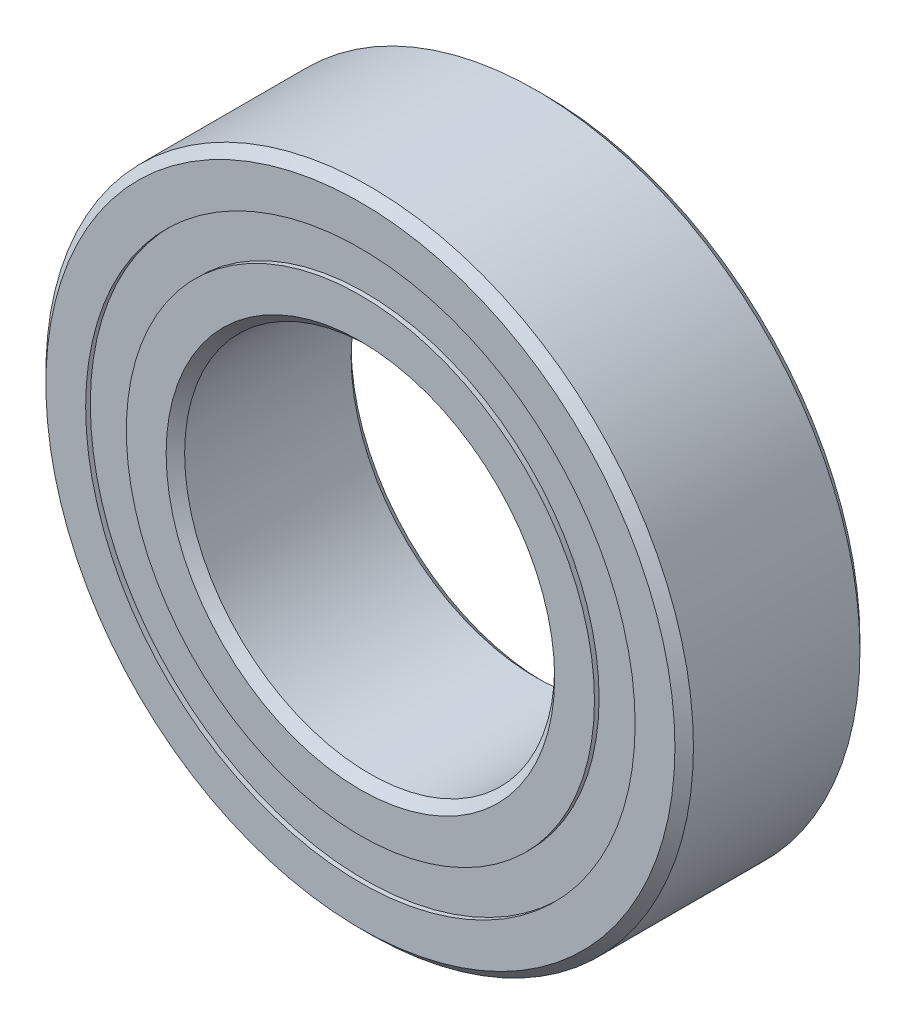
SolidWorks part; units mm, degrees
material "AISI 1015 Steel, Cold Drawn (SS)"
ref_plane "Front Plane" through (0, 0, 0) normal (0, 0, 1) x (1, 0, 0)
ref_plane "Top Plane" through (0, 0, 0) normal (0, 1, 0) x (1, 0, 0)
ref_plane "Right Plane" through (0, 0, 0) normal (1, 0, 0) x (0, 0, -1)
sketch "Sketch1" plane through (0, 0, 0) normal (1, 0, 0) x (0, 0, -1)
  line L0 (-2, 0) -> (2, 0) construction
  line L1 (0, 7) -> (0, -7) construction
  line L2 (1.8, 7) -> (-1.8, 7)
  line L3 (-1.8, 7) -> (-2, 6.8)
  line L4 (-2, 6.8) -> (-2, 5.9396)
  line L5 (-2, 5.9396) -> (-0.8889, 5.9396)
  line L6 (2, 5.9396) -> (0.8889, 5.9396)
  line L7 (2, 6.8) -> (2, 5.9396)
  line L8 (1.8, 7) -> (2, 6.8)
  line L9 (0, 7) -> (0, 5.5) construction
  line L10 (0, 5.5) -> (0, 4) construction
  arc A0 (-0.8889, 5.9396) -> (0.8889, 5.9396) centre (0, 5.5) cw
  point P14 (0, 4)
  dimension "D3" = 1.7778
  dimension "D1" = 45
  dimension "Width" = 4
  dimension "OD" = 14
  dimension "D2" = 0.2
  dimension "Shaft Dia" = 8
  dimension "D4" = 0.4396
revolve "Revolve1" add sketch "Sketch1" angle 360 about L0
sketch "Sketch3" plane through (0, 0, 0) normal (1, 0, 0) x (0, 0, -1)
  line L0 (-2, 5.0604) -> (-0.8889, 5.0604)
  line L1 (0, 7) -> (0, -7) construction
  line L2 (-2, 6.8) -> (-2, 5.9396) construction
  line L3 (-2, 5.0604) -> (-2, 4.2)
  line L4 (-1.8, 7) -> (-2, 6.8) construction
  line L5 (-2, 4.2) -> (-1.8, 4)
  line L6 (-1.8, 4) -> (1.8, 4)
  line L7 (1.8, 7) -> (1.8, -7) construction
  line L8 (1.8, 4) -> (2, 4.2)
  line L9 (2, -6.8) -> (2, 6.8) construction
  line L10 (2, 4.2) -> (2, 5.0604)
  line L11 (2, 5.0604) -> (0.8889, 5.0604)
  line L13 (1.8, 7) -> (2, 6.8) construction
  arc A0 (0.8889, 5.9396) -> (-0.8889, 5.9396) centre (0, 5.5) ccw construction
  arc A1 (0.8889, 5.0604) -> (-0.8889, 5.0604) centre (0, 5.5) cw
revolve "Revolve3" add sketch "Sketch3" angle 360 about L0
sketch "Sketch4" plane through (0, 0, 0) normal (1, 0, 0) x (0, 0, -1)
  line L0 (-0.9916, 5.5) -> (0.9916, 5.5)
  arc A2 (-0.9916, 5.5) -> (0.9916, 5.5) centre (0, 5.5) cw
  arc A3 (0.8889, 5.9396) -> (-0.8889, 5.9396) centre (0, 5.5) ccw construction
revolve "Revolve4" add sketch "Sketch4" angle 360 about L0
ref_axis "Axis1" through (0, 0, -2) along (0, 0, 1)
pattern_circular "CirPattern1" count 12 every 30 about axis through (0, 0, -2) along (0, 0, 1) of bodies 104
sketch "Sketch5" plane through (0, 0, 0) normal (1, 0, 0) x (0, 0, -1)
  line L0 (-2, 5.9396) -> (-0.8889, 5.9396) construction
  line L1 (-1.9, 5.9396) -> (-0.9916, 5.9396)
  line L2 (-1.9, 5.9396) -> (-1.9, 5.0604)
  line L3 (-1.9, 5.0604) -> (-0.9916, 5.0604)
  line L4 (-0.9916, 5.9396) -> (-0.9916, 5.0604)
  line L5 (-2, 5.0604) -> (-0.8889, 5.0604) construction
  line L6 (2, 5.9396) -> (0.8889, 5.9396) construction
  line L7 (1.9, 5.9396) -> (0.9916, 5.9396)
  line L8 (1.9, 5.9396) -> (1.9, 5.0604)
  line L9 (1.9, 5.0604) -> (0.9916, 5.0604)
  line L10 (0.9916, 5.9396) -> (0.9916, 5.0604)
  line L11 (2, 5.0604) -> (0.8889, 5.0604) construction
  line L12 (-1.8, 7) -> (-2, 6.8) construction
  point P18 (-1.9, 6.9)
revolve "Revolve5" add sketch "Sketch5" angle 360 about L0
sketch "Sketch6" plane through (0, 0, 0) normal (1, 0, 0) x (0, 0, -1)
  line L0 (2, 0) -> (-2, 0) construction
  line L1 (2, 5.9396) -> (1.2126, 5.9396)
  line L2 (2, 5.9396) -> (2, 6.9469)
  line L3 (2, 6.9469) -> (1.2126, 6.9469)
  line L4 (1.2126, 5.9396) -> (1.2126, 6.9469)
  dimension "Th" = 0.7874
  dimension "Flange OD" = 13.8938
revolve "Revolve6" [suppressed] add sketch "Sketch6" angle 360 about L0
equation "\"D2@Sketch1\" = \"Width@Sketch1\"*.05"
equation "\"D3@Sketch1\" = \"Width@Sketch1\"/2.25"
equation "\"D4@Sketch1\" = (((\"OD@Sketch1\"-\"Width@Sketch1\")/2)/3.25)/3.5"
equation "\"D2@CirPattern1\" = 360/\"Balls@CirPattern1\""
